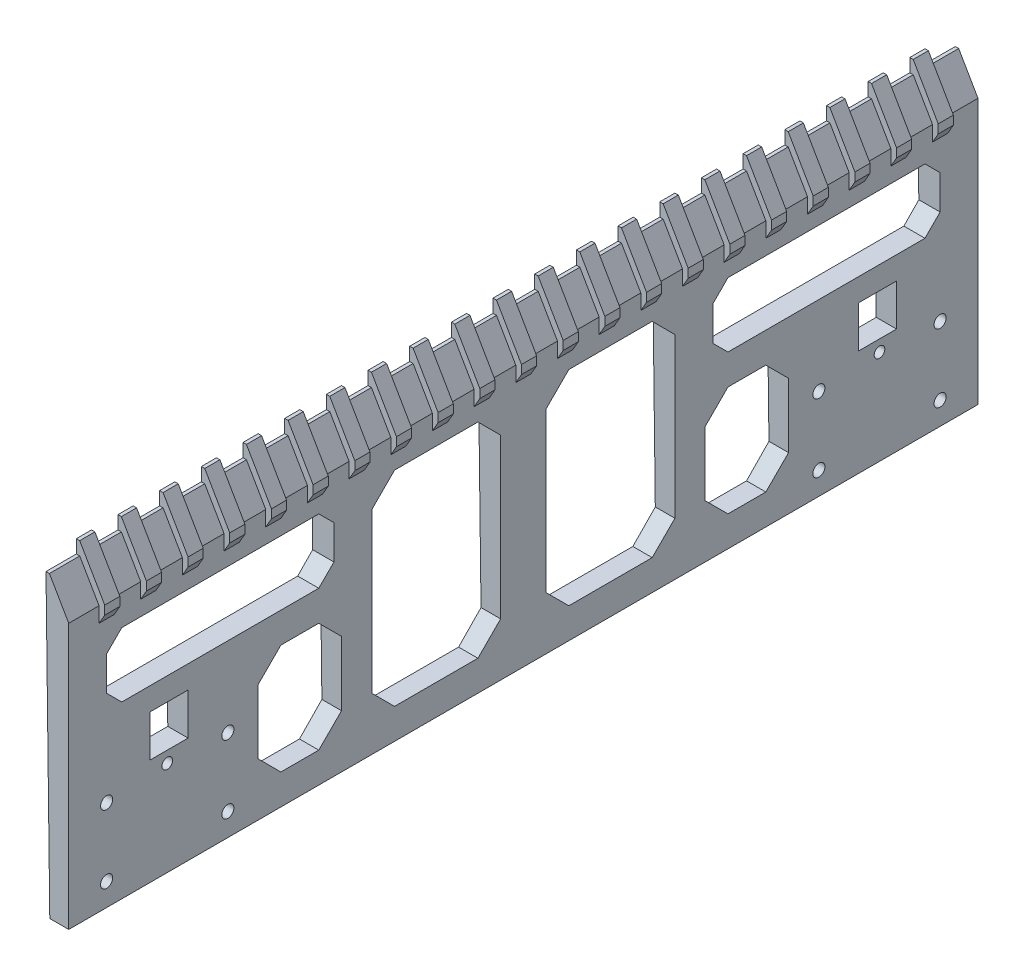
SolidWorks part; units mm, degrees
ref_plane "前视基准面" through (0, 0, 0) normal (0, 0, 1) x (1, 0, 0)
ref_plane "上视基准面" through (0, 0, 0) normal (0, 1, 0) x (1, 0, 0)
ref_plane "右视基准面" through (0, 0, 0) normal (1, 0, 0) x (0, 0, -1)
sketch "草图1" plane through (0, 0, 0) normal (1, 0, 0) x (0, 0, -1)
  line L1 (0, 0) -> (240, 0)
  line L2 (0, 0) -> (0, -70)
  line L3 (0, -70) -> (240, -70)
  line L4 (240, 0) -> (240, -70)
  dimension "D1" = 240
  dimension "D2" = 70
extrude "凸台-拉伸1" add sketch "草图1" along normal blind 6
sketch "草图3" plane through (6, 0, 0) normal (1, 0, 0) x (0, 0, -1)
  line L0 (120, 0) -> (120, -70) construction
  line L1 (14, -8) -> (66, -8)
  line L2 (10, -12) -> (10, -21)
  line L3 (14, -25) -> (66, -25)
  line L4 (70, -12) -> (70, -21)
  line L5 (240, 0) -> (0, 0) construction
  line L6 (0, -70) -> (240, -70) construction
  line L7 (0, 0) -> (0, -70) construction
  line L12 (10, -12) -> (14, -8)
  line L13 (10, -21) -> (14, -25)
  line L14 (66, -25) -> (70, -21)
  line L15 (66, -8) -> (70, -12)
  line L28 (80, -14) -> (86, -8)
  line L36 (50, -56) -> (56, -62)
  line L42 (86, -8) -> (108, -8)
  line L43 (80, -14) -> (80, -56)
  line L44 (86, -62) -> (108, -62)
  line L45 (114, -14) -> (114, -56)
  line L46 (108, -8) -> (114, -14)
  line L47 (108, -62) -> (114, -56)
  line L48 (80, -56) -> (86, -62)
  line L49 (56, -33) -> (66, -33)
  line L50 (50, -39) -> (50, -56)
  line L51 (56, -62) -> (66, -62)
  line L52 (72, -39) -> (72, -56)
  line L53 (66, -62) -> (72, -56)
  line L54 (66, -33) -> (72, -39)
  line L55 (50, -39) -> (56, -33)
  point P0 (10, -8)
  point P1 (70, -25)
  point P2 (10, -25)
  point P3 (70, -8)
  point P20 (80, -8)
  point P21 (114, -62)
  point P22 (80, -62)
  point P23 (114, -8)
  point P24 (50, -33)
  point P33 (72, -62)
  point P34 (50, -62)
  point P35 (72, -33)
  dimension "D1" = 10
  dimension "D2" = 8
  dimension "D3" = 17
  dimension "D4" = 60
  dimension "D5" = 8
  dimension "D6" = 8
  dimension "D7" = 54
  dimension "D12" = 80
  dimension "D13" = 6
  dimension "D14" = 34
  dimension "D15" = 10
  dimension "D16" = 8
  dimension "D21" = 8
  dimension "D22" = 29
  dimension "D23" = 22
extrude "切除-拉伸2" cut sketch "草图3" against normal through all
sketch "草图2" plane through (0, 0, 0) normal (1, 0, 0) x (0, 0, -1)
  line L1 (10, -46) -> (42, -46) construction
  line L2 (10, -46) -> (10, -64) construction
  line L3 (10, -64) -> (42, -64) construction
  line L4 (42, -46) -> (42, -64) construction
  line L5 (240, 0) -> (0, 0) construction
  line L6 (120, 0) -> (120, -70) construction
  line L7 (26, -27.5794) -> (26, -70.3864) construction
  line L8 (26, -27.5794) -> (26, -70.3864) construction
  circle A0 centre (10, -46) radius 1.55
  circle A1 centre (42, -64) radius 1.55
  circle A2 centre (42, -46) radius 1.55
  circle A3 centre (10, -64) radius 1.55
  dimension "D5" = 3.1
  dimension "D2" = 46
  dimension "D3" = 32
  dimension "D4" = 18
sketch "草图6" plane through (0, 0, 0) normal (0, 0, 1) x (1, 0, 0)
  line L0 (6, 0) -> (0, 0)
  line L1 (0, 0) -> (0, 8.8335)
  line L2 (0.9, 8.8335) -> (6, 0)
  line L3 (0, 8.8335) -> (0.9, 8.8335)
  line L4 (0, 8.8335) -> (0, 10.3923) construction
  line L5 (0, 10.3923) -> (0.9, 8.8335) construction
  dimension "D1" = 30
  dimension "D2" = 0.9
extrude "凸台-拉伸2" add sketch "草图6" against normal blind 240
ref_plane "基准面1" through (0, 0, -120) normal (0, 0, 1) x (1, 0, 0)
sketch "草图8" plane through (0, 0, -120) normal (0, 0, 1) x (1, 0, 0)
  line L0 (0, 10.3923) -> (0, 12.3335)
  line L1 (0.9, 12.3335) -> (7.5, 0.9019)
  line L2 (7.5, 0.9019) -> (7.5, -1.4019)
  line L3 (7.5, -4) -> (6, -4) construction
  line L4 (6, 0) -> (6, -70) construction
  line L5 (6, -4) -> (6, 0)
  line L6 (6, 0) -> (0.9, 8.8335) construction
  line L7 (6, 0) -> (0.9, 8.8335)
  line L8 (0, 12.3335) -> (0.9, 12.3335)
  line L9 (0, 12.3335) -> (0, 13.8923) construction
  line L10 (0, 13.8923) -> (0.9, 12.3335) construction
  line L11 (0, 10.3923) -> (0, 8.8335)
  line L12 (0, 8.8335) -> (0.9, 8.8335)
  line L13 (0.9, 8.8335) -> (0, 10.3923) construction
  line L14 (6, -4) -> (7.5, -1.4019)
  line L15 (7.5, -1.4019) -> (7.5, -4) construction
  dimension "D1" = 3.5
  dimension "D2" = 1.5
  dimension "D3" = 4
  dimension "D4" = 0.9
  dimension "D5" = 30
extrude "凸台-拉伸3" add sketch "草图8" along normal mid plane 4
pattern_linear "阵列(线性)1" count 11 spacing 11 along (0, 0, 1) count 11 spacing 11 along (0, 0, -1) of "凸台-拉伸3"
hole_wizard "打孔尺寸(%根据)内六角圆柱头螺钉的类型1" positions "草图14" profile "草图15" counterbore size "M3" standard "GB" end condition through all
sketch "草图14" plane through (0, 0, 0) normal (-1, 0, 0) x (0, 0, 1)
  point P0 (-42, -46)
  point P3 (-10, -46)
  point P6 (-10, -64)
  point P9 (-42, -64)
sketch "草图15" plane through (0, -46, -42) normal (0, 1, 0) x (0, 0, 1)
  line L0 (0, 0) -> (0, 7.5)
  line L1 (0, 7.5) -> (1.6, 7.5)
  line L3 (1.6, 7.5) -> (1.6, 3.4)
  line L4 (1.6, 3.4) -> (3, 3.4)
  line L5 (3, 3.4) -> (3, 0)
  line L7 (3, 0) -> (0, 0)
  line L11 (0, -6.35) -> (0, 107.95) construction
  dimension "通孔孔直径" = 3.2
  dimension "通孔孔深度" = 7.5
  dimension "柱形沉头孔直径" = 6
  dimension "柱形沉头孔深度" = 3.4
sketch "草图16" plane through (0, 0, 0) normal (-1, 0, 0) x (0, 0, 1)
  line L0 (-10, -46) -> (-42, -46) construction
  line L1 (-26, -46) -> (-26, -25) construction
  line L2 (-14, -25) -> (-66, -25) construction
  line L3 (-26, -46) -> (-26, -70) construction
  line L4 (0, -70) -> (-240, -70) construction
  circle A0 centre (-26, -45.0233) radius 1.4
  dimension "D1" = 2.8
extrude "切除-拉伸3" cut sketch "草图16" against normal blind 10
mirror "镜向1" about plane through (0, 0, -120) normal (0, 0, 1) of "打孔尺寸(%根据)内六角圆柱头螺钉的类型1"
mirror "镜向2" about plane through (0, 0, -120) normal (0, 0, 1) of "切除-拉伸3", "切除-拉伸2"
sketch "草图17" plane through (0, 0, 0) normal (-1, 0, 0) x (0, 0, 1)
  line L0 (0, 8.8335) -> (0, -70) construction
  line L1 (-31.5, -31) -> (-21.5, -31)
  line L2 (-31.5, -31) -> (-31.5, -42)
  line L3 (-31.5, -42) -> (-21.5, -42)
  line L4 (-21.5, -31) -> (-21.5, -42)
  line L6 (0, -70) -> (-240, -70) construction
  line L7 (-120, -70) -> (-120, -8.018) construction
  line L8 (-208.5, -31) -> (-218.5, -31)
  line L9 (-208.5, -31) -> (-208.5, -42)
  line L10 (-208.5, -42) -> (-218.5, -42)
  line L11 (-218.5, -31) -> (-218.5, -42)
  dimension "D1" = 10
  dimension "D2" = 11
  dimension "D3" = 21.5
  dimension "D4" = 28
extrude "切除-拉伸4" cut sketch "草图17" against normal through all
sketch "草图18" plane through (0, 0, 0) normal (0, 0, 1) x (1, 0, 0)
  line L0 (0, -70) -> (1, -70)
  line L1 (6, -70) -> (0, -70) construction
  line L4 (1, -70) -> (0, 8.8335)
  line L5 (0, 8.8335) -> (0, -70)
  dimension "D1" = 1
extrude "切除-拉伸5" cut sketch "草图18" against normal up to next
